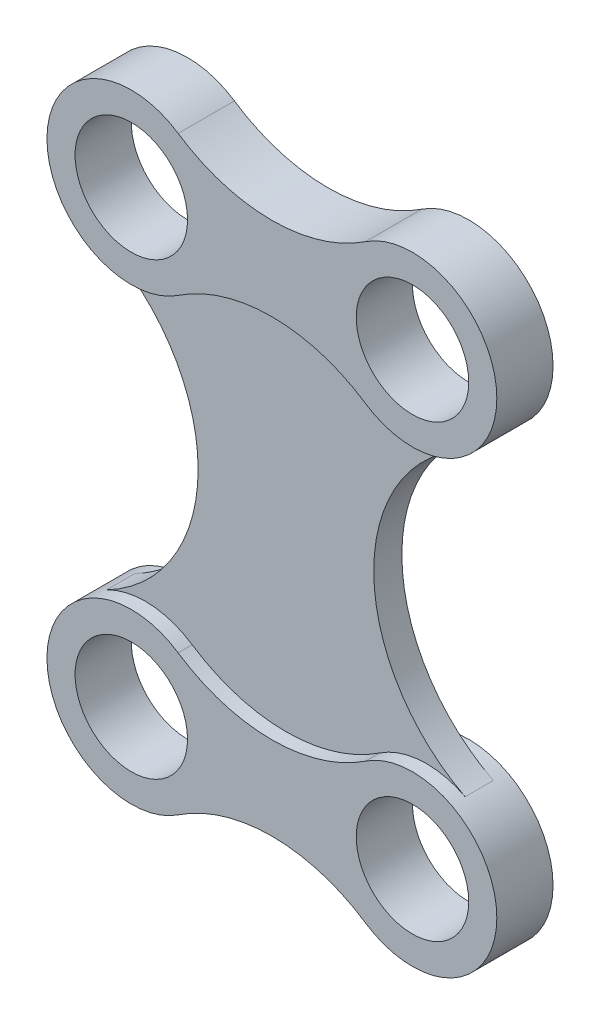
SolidWorks part; units mm, degrees
ref_plane "Front Plane" through (0, 0, 0) normal (0, 0, 1) x (1, 0, 0)
ref_plane "Top Plane" through (0, 0, 0) normal (0, 1, 0) x (1, 0, 0)
ref_plane "Right Plane" through (0, 0, 0) normal (1, 0, 0) x (0, 0, -1)
sketch "Sketch1" plane through (0, 0, 0) normal (0, 0, 1) x (1, 0, 0)
  line L0 (-25, 40) -> (25, 40) construction
  line L1 (-13.6379, 0) -> (12.2707, 0) construction
  line L2 (-25, -40) -> (25, -40) construction
  line L3 (0, 15.8636) -> (0, -20.4283) construction
  circle A0 centre (-25, 40) radius 10
  circle A1 centre (25, 40) radius 10
  arc A2 (16.6667, 27.5278) -> (16.6667, 52.4722) centre (25, 40) ccw
  arc A3 (-16.6667, 52.4722) -> (-16.6667, 27.5278) centre (-25, 40) ccw
  arc A4 (-16.6667, 52.4722) -> (16.6667, 52.4722) centre (0, 77.4166) ccw
  arc A5 (-16.6667, 27.5278) -> (16.6667, 27.5278) centre (0, 2.5834) cw
  arc A6 (-16.6667, -27.5278) -> (16.6667, -27.5278) centre (0, -2.5834) ccw
  arc A7 (-16.6667, -52.4722) -> (16.6667, -52.4722) centre (0, -77.4166) cw
  arc A8 (-16.6667, -52.4722) -> (-16.6667, -27.5278) centre (-25, -40) cw
  arc A9 (16.6667, -27.5278) -> (16.6667, -52.4722) centre (25, -40) cw
  circle A10 centre (25, -40) radius 10
  circle A11 centre (-25, -40) radius 10
  arc A12 (-31.8718, 26.6667) -> (-31.8718, -26.6667) centre (-45.6155, 0) cw
  arc A13 (31.8718, 26.6667) -> (31.8718, -26.6667) centre (45.6155, 0) ccw
  point P4 (0, 40)
  dimension "D1" = 20
  dimension "D3" = 30
  dimension "D4" = 30
  dimension "D5" = 40
  dimension "D6" = 30
  dimension "D2" = 50
extrude "Boss-Extrude1" add sketch "Sketch1" along normal mid plane 10 contours A3 A5 A2 A4 A0 A1 | A9 A6 A8 A7 A10 A11 region at (0, 40, 0) region at (0, -40, 0)
extrude "Boss-Extrude2" add sketch "Sketch1<3>" along normal mid plane 5 contours A13 A2 A5 A3 A12 A8 A6 A9 region at (0, 0, 0)
sketch "Sketch1<3>" plane through (0, 0, 0) normal (0, 0, 1) x (1, 0, 0) same geometry as "Sketch1"
